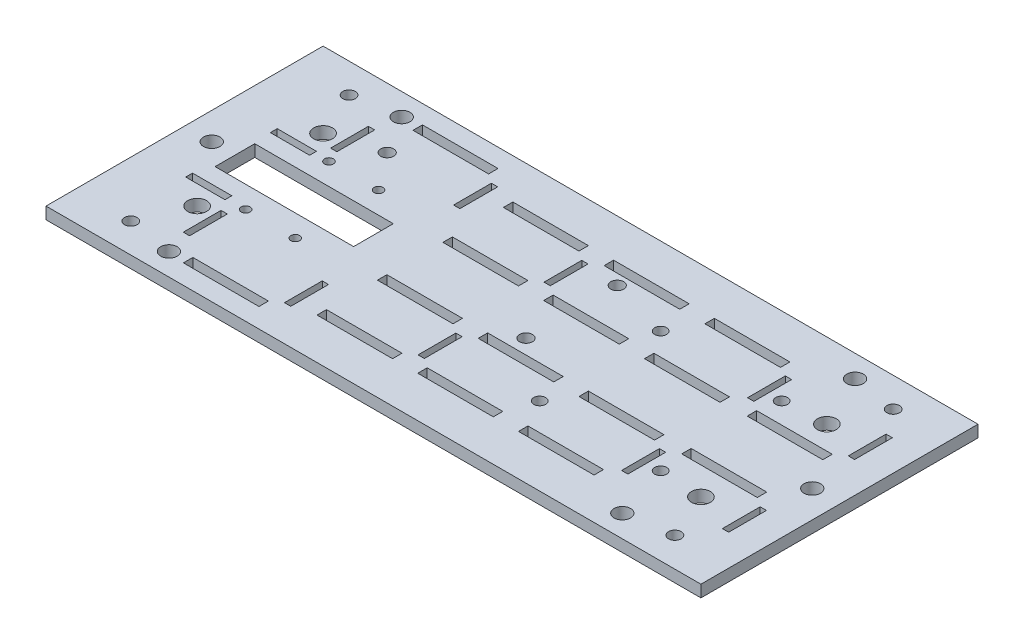
SolidWorks part; units mm, degrees
material "Thornel VCB-20 Carbon Cloth"
ref_plane "Front Plane" through (0, 0, 0) normal (0, 0, 1) x (1, 0, 0)
ref_plane "Top Plane" through (0, 0, 0) normal (0, 1, 0) x (1, 0, 0)
ref_plane "Right Plane" through (0, 0, 0) normal (1, 0, 0) x (0, 0, -1)
sketch "Sketch1" plane through (0, 0, 0) normal (0, 1, 0) x (1, 0, 0)
  line L0 (82.55, -34.925) -> (82.55, 34.925)
  line L1 (82.55, -34.925) -> (-82.55, -34.925)
  line L2 (82.55, 34.925) -> (-82.55, 34.925)
  line L3 (-82.55, -34.925) -> (-82.55, 34.925)
  line L4 (82.55, -34.925) -> (-82.55, 34.925) construction
  line L5 (82.55, 34.925) -> (-82.55, -34.925) construction
  point P1 (0, 0)
  dimension "D1" = 165.1
  dimension "D2" = 69.85
extrude "Boss-Extrude1" add sketch "Sketch1" along normal blind 3
sketch "Sketch6" plane through (0, 0, 0) normal (0, -1, 0) x (1, 0, 0)
  line L0 (-82.55, -34.925) -> (-82.55, 34.925) construction
  line L1 (-69.85, 5) -> (-34.925, 5)
  line L2 (-69.85, 5) -> (-69.85, -5)
  line L3 (-69.85, -5) -> (-34.925, -5)
  line L4 (-34.925, 5) -> (-34.925, -5)
  line L5 (6.775, -19.756) -> (-51.225, -19.756) construction
  line L6 (6.775, -19.756) -> (6.775, 3.246) construction
  line L7 (6.775, 3.246) -> (-51.225, 3.246) construction
  line L8 (-51.225, -19.756) -> (-51.225, 3.246) construction
  line L9 (6.775, -19.756) -> (-51.225, 3.246) construction
  line L10 (6.775, 3.246) -> (-51.225, -19.756) construction
  circle A0 centre (22.225, 15.25) radius 1.5
  circle A1 centre (52.725, 15.25) radius 1.5
  circle A2 centre (22.225, -15.25) radius 1.5
  circle A3 centre (52.725, -15.25) radius 1.5
  circle A4 centre (-51.225, 3.246) radius 1.625
  circle A5 centre (6.775, 3.246) radius 1.625
  circle A6 centre (6.775, -19.756) radius 1.625
  circle A7 centre (-51.225, -19.756) radius 1.625
  point P8 (-34.925, 0)
  point P18 (-22.225, -8.255)
  dimension "D5" = 3
  dimension "D6" = 3
  dimension "D7" = 3
  dimension "D8" = 3
  dimension "D18" = 3.25
  dimension "D1" = 34.925
  dimension "D2" = 10
  dimension "D3" = 12.7
  dimension "D4" = 30.5
  dimension "D9" = 30.5
  dimension "D10" = 30.5
  dimension "D11" = 15.25
  dimension "D12" = 22.225
  dimension "D13" = 15.25
  dimension "D14" = 15.25
  dimension "D15" = 15.25
  dimension "D16" = 23.002
  dimension "D17" = 58
  dimension "D19" = 60.325
  dimension "D20" = 8.255
extrude "Cut-Extrude1" cut sketch "Sketch6" against normal up to next contours A4 | L4 L1 L2 L3 A4 | A6 | A2 | A3 | A1 | A0 | A7 | A5 region at (-52.4158, 0, -0.079) region at (22.225, 0, 15.25) region at (52.725, 0, 15.25) region at (22.225, 0, -15.25) region at (52.725, 0, -15.25) region at (-51.225, 0, 3.246) region at (6.775, 0, -19.756)
sketch "Sketch7" plane through (0, 3, 0) normal (0, 1, 0) x (1, 0, 0)
  line L0 (-82.55, 34.925) -> (-82.55, -34.925) construction
  line L1 (82.55, -34.925) -> (82.55, 34.925) construction
  line L2 (-82.55, -34.925) -> (82.55, -34.925) construction
  line L3 (82.55, 34.925) -> (-82.55, 34.925) construction
  circle A0 centre (-77.47, 29.845) radius 1.5
  circle A1 centre (-77.47, -29.845) radius 1.5
  circle A2 centre (77.47, -29.845) radius 1.5
  circle A3 centre (77.47, 29.845) radius 1.5
  dimension "D9" = 3
  dimension "D10" = 3
  dimension "D11" = 3
  dimension "D12" = 3
  dimension "D1" = 5.08
  dimension "D2" = 5.08
  dimension "D3" = 5.08
  dimension "D4" = 5.08
  dimension "D5" = 5.08
  dimension "D6" = 5.08
  dimension "D7" = 5.08
  dimension "D8" = 5.08
sketch "Sketch8" plane through (0, 3, 0) normal (0, 1, 0) x (1, 0, 0)
  line L0 (-82.55, -34.925) -> (82.55, -34.925) construction
  line L1 (-82.55, 34.925) -> (-82.55, -34.925) construction
  line L2 (82.55, -34.925) -> (82.55, 34.925) construction
  line L3 (82.55, 34.925) -> (-82.55, 34.925) construction
  circle A0 centre (-63.5, -15.875) radius 2.3813
  circle A1 centre (-63.5, 15.875) radius 2.3813
  circle A2 centre (63.5, 15.875) radius 2.3813
  circle A3 centre (63.5, -15.875) radius 2.3813
  dimension "D1" = 4.7625
  dimension "D4" = 4.7625
  dimension "D5" = 4.7625
  dimension "D6" = 4.7625
  dimension "D2" = 19.05
  dimension "D3" = 19.05
  dimension "D7" = 19.05
  dimension "D8" = 19.05
  dimension "D9" = 19.05
  dimension "D10" = 19.05
  dimension "D11" = 19.05
  dimension "D12" = 19.05
extrude "Cut-Extrude3" cut sketch "Sketch8" against normal up to next
sketch "Sketch9" plane through (0, 3, 0) normal (0, 1, 0) x (1, 0, 0)
  line L0 (-82.55, 34.925) -> (-82.55, -34.925) construction
  line L1 (82.55, -34.925) -> (82.55, 34.925) construction
  circle A0 centre (-75.692, 0) radius 2.0828
  circle A1 centre (75.692, 0) radius 2.0828
  dimension "D1" = 6.858
  dimension "D2" = 6.858
extrude "Cut-Extrude5" cut sketch "Sketch9" against normal blind 5.08
sketch "Sketch10" plane through (0, 3, 0) normal (0, 1, 0) x (1, 0, 0)
  line L0 (-82.55, -34.925) -> (82.55, -34.925) construction
  line L1 (82.55, 34.925) -> (-82.55, 34.925) construction
  circle A0 centre (0, -29.337) radius 2.0828
  circle A1 centre (0, 29.337) radius 2.0828
  circle A2 centre (57.15, -29.337) radius 2.0828
  circle A3 centre (57.15, 29.337) radius 2.0828
  circle A4 centre (-57.15, -29.337) radius 2.0828
  circle A5 centre (-57.15, 29.337) radius 2.0828
  dimension "D1" = 5.588
  dimension "D2" = 5.588
  dimension "D3" = 2
  dimension "D4" = 2
extrude "Cut-Extrude6" cut sketch "Sketch10" against normal blind 5.08 contours A5 | A2 | A3 | A4 region at (57.15, 3, 29.337) region at (57.15, 3, -29.337) region at (-57.15, 3, 29.337) region at (-57.15, 3, -29.337)
sketch "Sketch11" plane through (0, 3, 0) normal (0, 1, 0) x (1, 0, 0)
  line L1 (-44.1375, 10.5) -> (-56.6375, 10.5) construction
  line L2 (-44.1375, 10.5) -> (-44.1375, -10.5) construction
  line L3 (-44.1375, -10.5) -> (-56.6375, -10.5) construction
  line L4 (-56.6375, 10.5) -> (-56.6375, -10.5) construction
  line L5 (-44.1375, 10.5) -> (-56.6375, -10.5) construction
  line L6 (-44.1375, -10.5) -> (-56.6375, 10.5) construction
  line L7 (-34.925, 5) -> (-69.85, 5) construction
  circle A0 centre (-56.6375, 10.5) radius 1.125
  circle A1 centre (-44.1375, 10.5) radius 1.125
  circle A2 centre (-44.1375, -10.5) radius 1.125
  circle A3 centre (-56.6375, -10.5) radius 1.125
  point P0 (-50.3875, 0)
  point P9 (-52.3875, 5)
  dimension "D4" = 2.25
  dimension "D5" = 2.25
  dimension "D6" = 2.25
  dimension "D7" = 2.25
  dimension "D1" = 12.5
  dimension "D2" = 21
  dimension "D3" = 2
extrude "Cut-Extrude7" cut sketch "Sketch11" against normal blind 41.91
sketch "Sketch12" plane through (0, 0, 0) normal (0, -1, 0) x (1, 0, 0)
  line L0 (-24.5963, 23.3735) -> (-5.5463, 23.3735) construction
  line L1 (-24.5963, 24.5641) -> (-5.5463, 24.5641)
  line L2 (-24.5963, 24.5641) -> (-24.5963, 22.1829)
  line L3 (-24.5963, 22.1829) -> (-5.5463, 22.1829)
  line L4 (-5.5463, 24.5641) -> (-5.5463, 22.1829)
  line L5 (-15.0713, 24.5641) -> (-15.0713, 22.1829)
  line L6 (0.8037, 24.5641) -> (0.8037, 22.1829)
  line L7 (0.8037, 24.5641) -> (19.8537, 24.5641)
  line L8 (19.8537, 24.5641) -> (19.8537, 22.1829)
  line L9 (0.8037, 22.1829) -> (19.8537, 22.1829)
  line L10 (26.2037, 24.5641) -> (26.2037, 22.1829)
  line L11 (26.2037, 24.5641) -> (45.2537, 24.5641)
  line L12 (45.2537, 24.5641) -> (45.2537, 22.1829)
  line L13 (26.2037, 22.1829) -> (45.2537, 22.1829)
  line L14 (0.8037, 9.3241) -> (0.8037, 6.9429)
  line L15 (0.8037, 9.3241) -> (19.8537, 9.3241)
  line L16 (19.8537, 9.3241) -> (19.8537, 6.9429)
  line L17 (0.8037, 6.9429) -> (19.8537, 6.9429)
  line L18 (26.2037, 9.3241) -> (26.2037, 6.9429)
  line L19 (26.2037, 9.3241) -> (45.2537, 9.3241)
  line L20 (45.2537, 9.3241) -> (45.2537, 6.9429)
  line L21 (26.2037, 6.9429) -> (45.2537, 6.9429)
  line L22 (-24.5963, 9.3241) -> (-24.5963, 6.9429)
  line L23 (-24.5963, 9.3241) -> (-5.5463, 9.3241)
  line L24 (-5.5463, 9.3241) -> (-5.5463, 6.9429)
  line L25 (-24.5963, 6.9429) -> (-5.5463, 6.9429)
  line L26 (-24.5963, 24.5641) -> (0.8037, 24.5641) construction
  line L27 (-71.2714, 9.2531) -> (-61.3765, 9.2531)
  line L28 (-24.5963, -24.8071) -> (0.8037, -24.8071) construction
  line L29 (-24.5963, -23.6165) -> (-5.5463, -23.6165) construction
  line L30 (-24.5963, -7.1859) -> (-5.5463, -7.1859)
  line L31 (-5.5463, -9.5671) -> (-5.5463, -7.1859)
  line L32 (-24.5963, -9.5671) -> (-5.5463, -9.5671)
  line L33 (-24.5963, -9.5671) -> (-24.5963, -7.1859)
  line L34 (26.2037, -7.1859) -> (45.2537, -7.1859)
  line L35 (45.2537, -9.5671) -> (45.2537, -7.1859)
  line L36 (26.2037, -9.5671) -> (45.2537, -9.5671)
  line L37 (26.2037, -9.5671) -> (26.2037, -7.1859)
  line L38 (0.8037, -7.1859) -> (19.8537, -7.1859)
  line L39 (19.8537, -9.5671) -> (19.8537, -7.1859)
  line L40 (0.8037, -9.5671) -> (19.8537, -9.5671)
  line L41 (0.8037, -9.5671) -> (0.8037, -7.1859)
  line L42 (26.2037, -22.4259) -> (45.2537, -22.4259)
  line L43 (45.2537, -24.8071) -> (45.2537, -22.4259)
  line L44 (26.2037, -24.8071) -> (45.2537, -24.8071)
  line L45 (26.2037, -24.8071) -> (26.2037, -22.4259)
  line L46 (0.8037, -22.4259) -> (19.8537, -22.4259)
  line L47 (19.8537, -24.8071) -> (19.8537, -22.4259)
  line L48 (0.8037, -24.8071) -> (19.8537, -24.8071)
  line L49 (0.8037, -24.8071) -> (0.8037, -22.4259)
  line L50 (-15.0713, -24.8071) -> (-15.0713, -22.4259)
  line L51 (-5.5463, -24.8071) -> (-5.5463, -22.4259)
  line L52 (-24.5963, -22.4259) -> (-5.5463, -22.4259)
  line L53 (-24.5963, -24.8071) -> (-24.5963, -22.4259)
  line L54 (-24.5963, -24.8071) -> (-5.5463, -24.8071)
  line L56 (-3.1651, 10.991) -> (-1.5776, 10.991)
  line L57 (-3.1651, 10.991) -> (-3.1651, 20.516)
  line L58 (-3.1651, 20.516) -> (-1.5776, 20.516)
  line L59 (-1.5776, 10.991) -> (-1.5776, 20.516)
  line L60 (-3.1651, 10.991) -> (-1.5776, 20.516) construction
  line L61 (-3.1651, 20.516) -> (-1.5776, 10.991) construction
  line L66 (-3.1651, -20.759) -> (-1.5776, -20.759)
  line L67 (-1.5776, -11.234) -> (-1.5776, -20.759)
  line L68 (-3.1651, -11.234) -> (-1.5776, -11.234)
  line L69 (-3.1651, -11.234) -> (-3.1651, -20.759)
  line L78 (51.6896, 8.9006) -> (51.6896, 6.5194)
  line L79 (51.6896, 8.9006) -> (70.7396, 8.9006)
  line L80 (70.7396, 8.9006) -> (70.7396, 6.5194)
  line L81 (51.6896, 6.5194) -> (70.7396, 6.5194)
  line L82 (-70.3121, -11.1231) -> (-60.4172, -11.1231)
  line L83 (64.3896, -0.545) -> (-18.1604, -0.545) construction
  line L84 (-70.3121, -11.1231) -> (-70.3121, -9.3903)
  line L85 (51.6896, -7.6094) -> (70.7396, -7.6094)
  line L86 (70.7396, -9.9906) -> (70.7396, -7.6094)
  line L87 (51.6896, -9.9906) -> (70.7396, -9.9906)
  line L88 (51.6896, -9.9906) -> (51.6896, -7.6094)
  line L93 (73.1208, 10.5675) -> (73.1208, 20.0925)
  line L94 (47.7208, 10.5675) -> (49.3083, 10.5675)
  line L95 (47.7208, 10.5675) -> (47.7208, 20.0925)
  line L96 (47.7208, 20.0925) -> (49.3083, 20.0925)
  line L97 (49.3083, 10.5675) -> (49.3083, 20.0925)
  line L98 (47.7208, 10.5675) -> (49.3083, 20.0925) construction
  line L99 (47.7208, 20.0925) -> (49.3083, 10.5675) construction
  line L100 (73.1208, 10.5675) -> (74.7083, 10.5675)
  line L101 (74.7083, 10.5675) -> (74.7083, 20.0925)
  line L102 (73.1208, 20.0925) -> (74.7083, 20.0925)
  line L103 (47.7208, 10.5675) -> (73.1208, 10.5675) construction
  line L104 (47.7208, -21.1825) -> (49.3083, -21.1825)
  line L105 (49.3083, -11.6575) -> (49.3083, -21.1825)
  line L106 (47.7208, -11.6575) -> (49.3083, -11.6575)
  line L107 (47.7208, -11.6575) -> (47.7208, -21.1825)
  line L108 (73.1208, -11.6575) -> (74.7083, -11.6575)
  line L109 (74.7083, -11.6575) -> (74.7083, -21.1825)
  line L110 (73.1208, -21.1825) -> (74.7083, -21.1825)
  line L111 (73.1208, -11.6575) -> (73.1208, -21.1825)
  line L112 (-70.3121, -9.3903) -> (-60.4172, -9.3903)
  line L113 (-60.4172, -11.1231) -> (-60.4172, -9.3903)
  line L114 (-52.8291, -27.8715) -> (-33.7791, -27.8715)
  line L115 (-33.7791, -30.2527) -> (-33.7791, -27.8715)
  line L116 (-52.8291, -30.2527) -> (-33.7791, -30.2527)
  line L117 (-52.8291, -30.2527) -> (-52.8291, -27.8715)
  line L118 (-70.3121, -11.1231) -> (-60.4172, -9.3903) construction
  line L123 (-59.3265, -23.1262) -> (-57.739, -23.1262)
  line L124 (-57.739, -13.6012) -> (-57.739, -23.1262)
  line L125 (-59.3265, -13.6012) -> (-57.739, -13.6012)
  line L126 (-59.3265, -13.6012) -> (-59.3265, -23.1262)
  line L127 (-31.3979, -16.6796) -> (-29.8104, -16.6796)
  line L128 (-29.8104, -16.6796) -> (-29.8104, -26.2046)
  line L129 (-31.3979, -26.2046) -> (-29.8104, -26.2046)
  line L130 (-31.3979, -16.6796) -> (-31.3979, -26.2046)
  line L131 (-70.3121, -9.3903) -> (-60.4172, -11.1231) construction
  line L132 (-71.2714, 9.2531) -> (-71.2714, 10.9859)
  line L133 (-31.3979, 16.4366) -> (-31.3979, 25.9616)
  line L134 (-31.3979, 25.9616) -> (-29.8104, 25.9616)
  line L135 (-29.8104, 16.4366) -> (-29.8104, 25.9616)
  line L136 (-31.3979, 16.4366) -> (-29.8104, 16.4366)
  line L137 (-59.5464, 13.798) -> (-59.5464, 23.323)
  line L138 (-59.5464, 13.798) -> (-57.9589, 13.798)
  line L139 (-57.9589, 13.798) -> (-57.9589, 23.323)
  line L140 (-59.5464, 23.323) -> (-57.9589, 23.323)
  line L145 (-71.2714, 10.9859) -> (-61.3765, 10.9859)
  line L146 (-52.8291, 30.0097) -> (-52.8291, 27.6285)
  line L147 (-52.8291, 30.0097) -> (-33.7791, 30.0097)
  line L148 (-33.7791, 30.0097) -> (-33.7791, 27.6285)
  line L149 (-52.8291, 27.6285) -> (-33.7791, 27.6285)
  line L150 (-61.3765, 9.2531) -> (-61.3765, 10.9859)
  point P8 (-65.3646, -10.2567)
  point P60 (-2.3713, 15.7535)
  point P100 (48.5146, 15.33)
  dimension "D1" = 19.05
  dimension "D2" = 2.3813
  dimension "D3" = 25.4
  dimension "D4" = 15.24
  dimension "D5" = 1.5875
  dimension "D6" = 3.175
  dimension "D7" = 9.525
  dimension "D8" = 7.62
extrude "Cut-Extrude8" cut sketch "Sketch12" against normal blind 21.336 contours L37 L36 L35 L34 | L88 L87 L86 L85 | L45 L44 L43 L42 | L117 L116 L115 L114 | L78 L81 L80 L79 | L10 L13 L12 L11 | L6 L9 L8 L7 | L14 L17 L16 L15 | L107 L104 L105 L106 | L109 L110 L111 L108 | L40 L39 L38 L41 | L48 L47 L46 L49 | L67 L66 L69 L68 | L52 L51 L54 L53 | L30 L31 L32 L33 | L130 L129 L128 L127 | L126 L123 L124 L125 | L93 L102 L101 L100 | L97 L96 L95 L94 | L19 L20 L21 L18 | L56 L59 L58 L57 | L25 L24 L23 L22 | L3 L4 L1 L2 | L135 L134 L133 L136 | L149 L148 L147 L146 | L139 L140 L137 L138 | L27 L150 L145 L132 | L84 L82 L113 L112 region at (10.3287, 0, 23.3735) region at (35.7287, 0, 23.3735) region at (10.3287, 0, 8.1335) region at (35.7287, 0, -8.3765) region at (35.7287, 0, -23.6165) region at (61.2146, 0, 7.71) region at (61.2146, 0, -8.8) region at (-43.3041, 0, -29.0621)
sketch "Sketch13" plane through (0, 0, 0) normal (0, -1, 0) x (1, 0, 0)
  line L0 (0, 18.4306) -> (0, -15.755) construction
  circle A0 centre (-68.5804, 27.5146) radius 1.5875 construction
  circle A1 centre (-68.5804, -27.5146) radius 1.5875 construction
  circle A2 centre (-68.5804, 27.5146) radius 1.5875
  circle A3 centre (-68.5804, -27.5146) radius 1.5875
  circle A4 centre (68.5804, -27.5146) radius 1.5875
  circle A5 centre (68.5804, 27.5146) radius 1.5875
extrude "Cut-Extrude10" cut sketch "Sketch13" against normal blind 28.034
